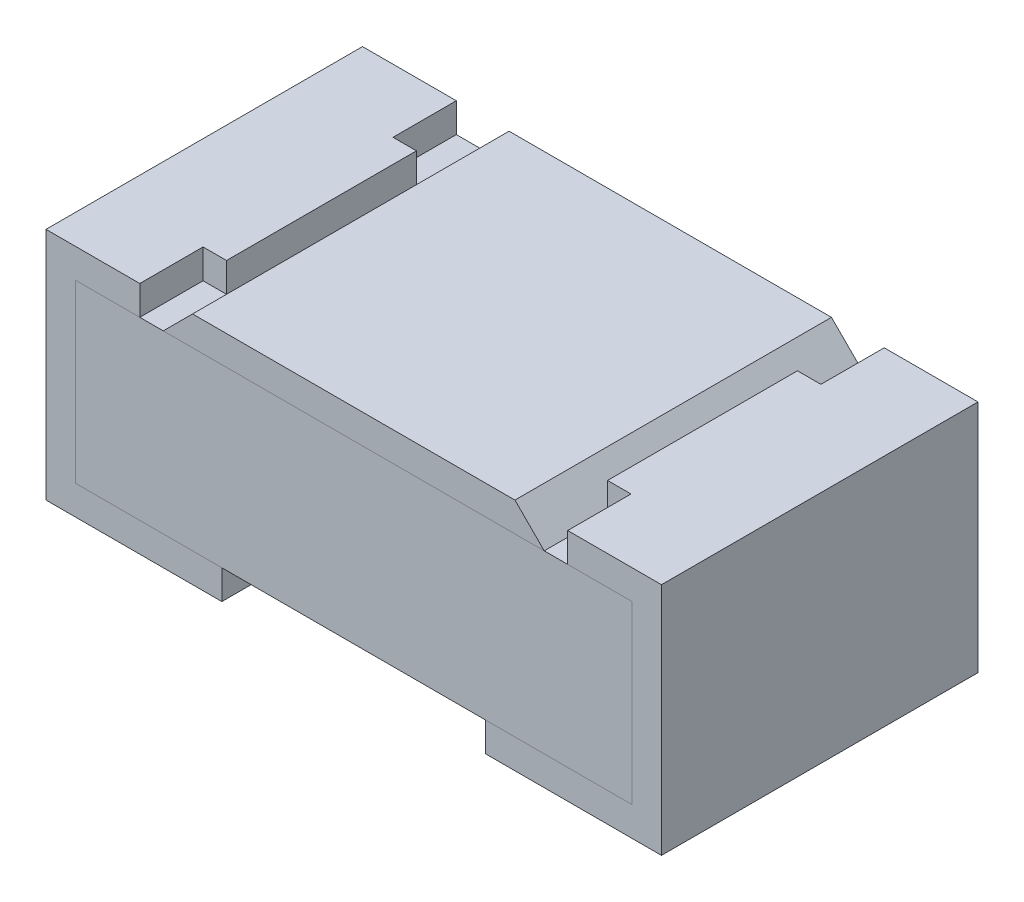
SolidWorks part; units mm, degrees
ref_plane "Спереди" through (0, 0, 0) normal (0, 0, 1) x (1, 0, 0)
ref_plane "Сверху" through (0, 0, 0) normal (0, 1, 0) x (1, 0, 0)
ref_plane "Справа" through (0, 0, 0) normal (1, 0, 0) x (0, 0, -1)
sketch "Эскиз1" plane through (0, 0, 0) normal (0, 1, 0) x (1, 0, 0)
  line L1 (-0.475, -0.27) -> (0.475, -0.27)
  line L2 (-0.475, -0.27) -> (-0.475, 0.27)
  line L3 (-0.475, 0.27) -> (0.475, 0.27)
  line L4 (0.475, -0.27) -> (0.475, 0.27)
  line L5 (-0.475, -0.27) -> (0.475, 0.27) construction
  line L6 (-0.475, 0.27) -> (0.475, -0.27) construction
  point P0 (0, 0)
  dimension "Длинна сопротивления" = 0.95
  dimension "Ширина резистора" = 0.54
sketch "Эскиз2" plane through (0, 0, 0) normal (0, 0, 1) x (1, 0, 0)
  line L0 (0, 0) -> (0, 0.05) construction
  line L1 (0, 0.05) -> (0, 0.35) construction
  line L2 (0, 0.35) -> (0, 0.4) construction
  dimension "Толщина металла" = 0.05
  dimension "Высота сопротивления" = 0.3
extrude "Бобышка-Вытянуть1" add sketch "Эскиз1" along normal up to vertex (0.35 mm away) from vertex up to point (0, 0.35, 0) starting at point (0, 0.05, 0)
sketch "Эскиз3" plane through (0, 0.35, 0) normal (0, 1, 0) x (1, 0, 0)
  line L0 (0.475, 0.27) -> (-0.475, 0.27) construction
  line L1 (0.325, -0.27) -> (-0.325, -0.27)
  line L2 (0.325, -0.27) -> (0.325, 0.27)
  line L3 (0.325, 0.27) -> (-0.325, 0.27)
  line L4 (-0.325, -0.27) -> (-0.325, 0.27)
  line L5 (0.325, -0.27) -> (-0.325, 0.27) construction
  line L6 (0.325, 0.27) -> (-0.325, -0.27) construction
  point P0 (0, 0)
  dimension "Длинна краски" = 0.65
extrude "Бобышка-Вытянуть2" add sketch "Эскиз3" along normal up to vertex (0.05 mm away) separate body up to point (0, 0.4, 0)
chamfer "Фаска1" distance 0.05 angle 45 2 edges at (-0.325, 0.4, 0) (0.325, 0.4, 0)
sketch "Эскиз4" plane through (0, 0, 0.27) normal (0, 0, 1) x (1, 0, 0)
  line L0 (-0.475, 0.05) -> (-0.525, 0.05) construction
  line L1 (0, 0) -> (0, 0.05) construction
  line L2 (-0.475, 0.05) -> (-0.475, 0) construction
  line L3 (-0.525, 0) -> (-0.525, 0.4)
  line L4 (-0.525, 0.4) -> (-0.325, 0.4)
  line L5 (-0.525, 0) -> (-0.225, 0)
  line L6 (-0.225, 0) -> (-0.225, 0.05)
  line L7 (-0.475, 0.05) -> (0.475, 0.05) construction
  line L8 (-0.225, 0.05) -> (-0.475, 0.05)
  line L9 (-0.475, 0.05) -> (-0.475, 0.35)
  line L10 (-0.475, 0.35) -> (-0.475, 0.05) construction
  line L11 (-0.325, 0.4) -> (-0.325, 0.35)
  line L12 (-0.475, 0.35) -> (0.475, 0.35) construction
  line L13 (-0.475, 0.35) -> (-0.325, 0.35)
  line L14 (0, 0.4) -> (0, 0) construction
  line L15 (0.225, 0.05) -> (0.475, 0.05)
  line L16 (0.225, 0) -> (0.225, 0.05)
  line L17 (0.525, 0) -> (0.225, 0)
  line L18 (0.525, 0) -> (0.525, 0.4)
  line L19 (0.525, 0.4) -> (0.325, 0.4)
  line L20 (0.325, 0.4) -> (0.325, 0.35)
  line L21 (0.475, 0.35) -> (0.325, 0.35)
  line L22 (0.475, 0.05) -> (0.475, 0.35)
  dimension "Высота" = 0.4
  dimension "Ширина контакта сверху" = 0.2
  dimension "Ширина контакта снизу" = 0.3
extrude "Бобышка-Вытянуть3" add sketch "Эскиз4" against normal up to surface (0.54 mm away) separate body up to face at (0, 0.2, -0.27)
sketch "Эскиз5" plane through (0, 0.4, 0) normal (0, 1, 0) x (1, 0, 0)
  line L0 (0, 0.217) -> (0, -0.217) construction
  line L1 (-0.3622, 0) -> (0.3622, 0) construction
  line L2 (0.325, 0.162) -> (0.365, 0.162)
  line L3 (-0.325, 0.27) -> (-0.365, 0.27)
  line L4 (-0.325, 0.27) -> (-0.325, 0.162)
  line L5 (-0.325, 0.162) -> (-0.365, 0.162)
  line L6 (-0.365, 0.27) -> (-0.365, 0.162)
  line L7 (0.365, 0.27) -> (0.365, 0.162)
  line L8 (0.325, 0.27) -> (0.365, 0.27)
  line L9 (0.325, 0.27) -> (0.325, 0.162)
  line L10 (-0.325, -0.162) -> (-0.365, -0.162)
  line L11 (-0.365, -0.27) -> (-0.365, -0.162)
  line L12 (-0.325, -0.27) -> (-0.365, -0.27)
  line L13 (-0.325, -0.27) -> (-0.325, -0.162)
  line L14 (0.325, -0.27) -> (0.325, -0.162)
  line L15 (0.325, -0.27) -> (0.365, -0.27)
  line L16 (0.365, -0.27) -> (0.365, -0.162)
  line L17 (0.325, -0.162) -> (0.365, -0.162)
  point P3 (0, 0)
  point P6 (0, 0)
  dimension "Длинна выреза контакта" = 0.04
  dimension "Ширина выреза контакта" = 0.108
extrude "Вырез-Вытянуть1" cut sketch "Эскиз5" against normal up to next (0.05 mm away)
